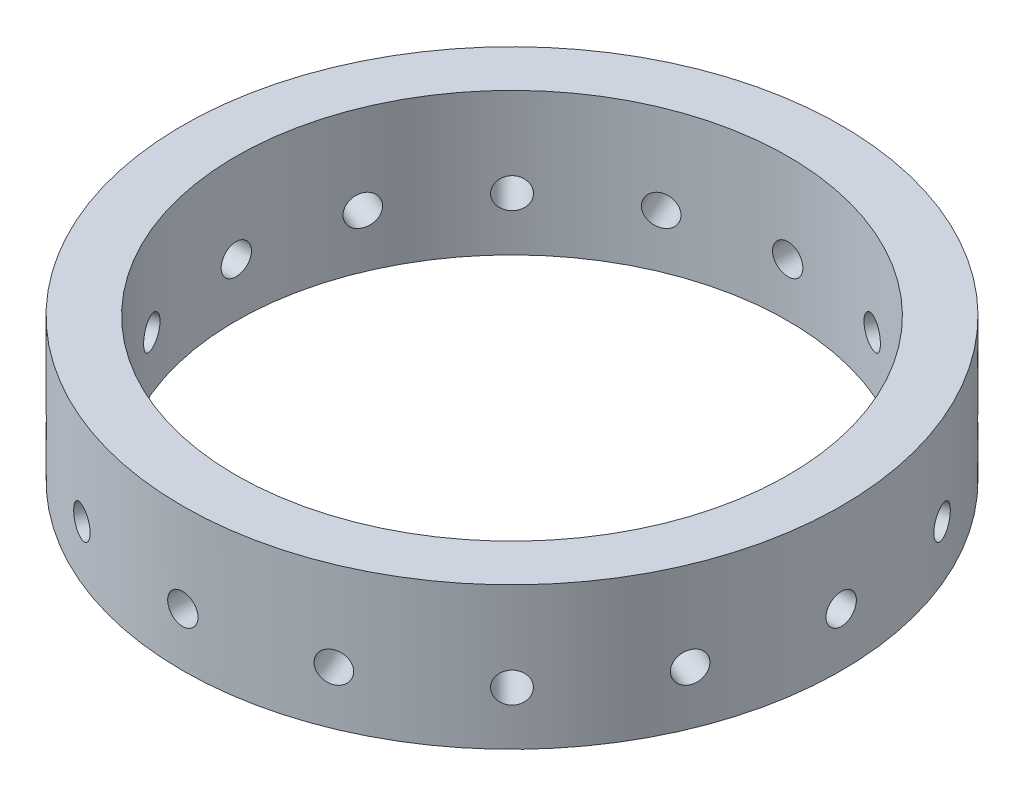
SolidWorks part; units mm, degrees
material "6061-T6 (SS)"
ref_plane "Front Plane" through (0, 0, 0) normal (0, 0, 1) x (1, 0, 0)
ref_plane "Top Plane" through (0, 0, 0) normal (0, 1, 0) x (1, 0, 0)
ref_plane "Right Plane" through (0, 0, 0) normal (1, 0, 0) x (0, 0, -1)
sketch "Sketch1" plane through (0, 0, 0) normal (0, 1, 0) x (1, 0, 0)
  circle A0 centre (0, 0) radius 58.7375
  circle A1 centre (0, 0) radius 49.2125
extrude "Boss-Extrude1" add sketch "Sketch1" along normal blind 25.4
ref_plane "Plane1" through (0, 0, -58.7375) normal (0, 0, -1) x (-1, 0, 0)
sketch "Sketch2" plane through (0, 0, -58.7375) normal (0, 0, -1) x (-1, 0, 0)
  line L0 (0, 0) -> (0, 9.525)
  point P4 (0, 9.525)
hole_wizard "Tap Drill for 1/4-28 Tap1" positions "Sketch3" profile "Sketch4" hole size "1/4-28" standard "ANSI Inch" end condition through all
sketch "Sketch3" plane through (0, 0, -58.7375) normal (0, 0, -1) x (-1, 0, 0)
  point P0 (0, 9.525)
sketch "Sketch4" plane through (0, 9.525, -58.7375) normal (1, 0, 0) x (0, 1, 0)
  line L0 (0, 0) -> (0, 117.475)
  line L1 (0, 117.475) -> (2.7051, 117.475)
  line L2 (2.7051, 117.475) -> (2.7051, 0)
  line L5 (2.7051, 0) -> (0, 0)
  line L11 (0, -6.35) -> (0, 107.95) construction
  dimension "Thru Hole Dia." = 5.4102
  dimension "Thru Hole Depth" = 117.475
sketch "Sketch5" plane through (0, 0, 0) normal (0, 0, 1) x (1, 0, 0)
  line L0 (0, 0) -> (0, 24.4952)
pattern_circular "CirPattern1" count 16 over 360 about axis through (0, 0, 0) along (0, 1, 0) of "Tap Drill for 1/4-28 Tap1" reverse direction yes
ref_plane "Plane2" through (0, 9.525, 0) normal (0, 1, 0) x (1, 0, 0)
